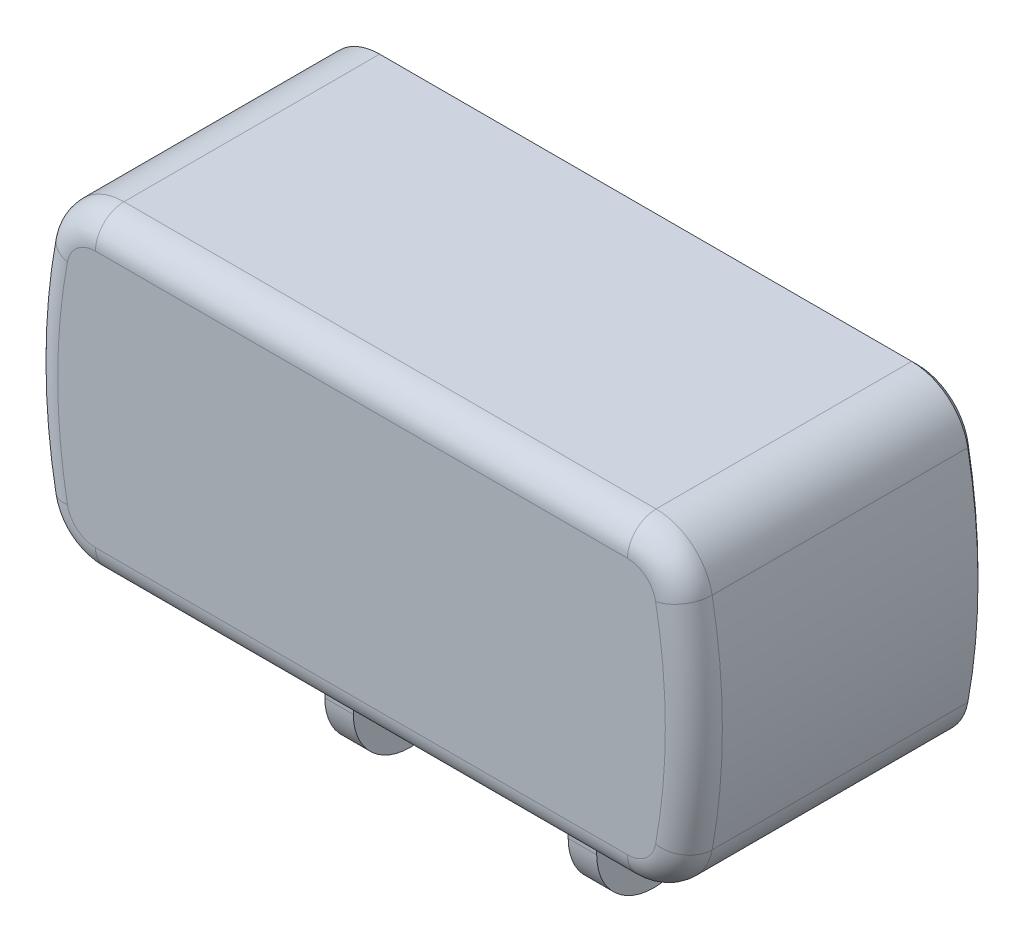
SolidWorks part; units mm, degrees
material "PLA"
ref_plane "Front Plane" through (0, 0, 0) normal (0, 0, 1) x (1, 0, 0)
ref_plane "Top Plane" through (0, 0, 0) normal (0, 1, 0) x (1, 0, 0)
ref_plane "Right Plane" through (0, 0, 0) normal (1, 0, 0) x (0, 0, -1)
sketch "Sketch2" plane through (0, 0, 0) normal (0, 0, 1) x (1, 0, 0)
  line L0 (-47.5, 0) -> (47.5, 0) construction
  line L1 (0, -27.5) -> (0, 27.5) construction
  line L2 (46.625, 27.5) -> (-46.625, 27.5)
  line L3 (46.625, -27.5) -> (-46.625, -27.5)
  arc A0 (-56.4565, 19.3279) -> (-56.4565, -19.3279) centre (47.5, 0) ccw
  arc A1 (-46.625, -27.5) -> (-56.4565, -19.3279) centre (-46.625, -17.5) cw
  arc A2 (-46.625, 27.5) -> (-56.4565, 19.3279) centre (-46.625, 17.5) ccw
  arc A3 (46.625, -27.5) -> (56.4565, -19.3279) centre (46.625, -17.5) ccw
  arc A4 (56.4565, 19.3279) -> (56.4565, -19.3279) centre (-47.5, 0) cw
  arc A5 (46.625, 27.5) -> (56.4565, 19.3279) centre (46.625, 17.5) cw
  point P4 (0, 0)
  point P8 (0, 0)
  dimension "D3" = 0
  dimension "D4" = 10
  dimension "D1" = 95
  dimension "D2" = 55
  dimension "D5" = 46.625
extrude "Boss-Extrude5" add sketch "Sketch2" along normal blind 50.8
fillet "Fillet9" radius 5 8 edges at (-58.238, 0, 50.8) (-53.0172, 25.1902, 50.8) (0, 27.5, 50.8) (53.0172, 25.1902, 50.8) (58.238, 0, 50.8) (53.0172, -25.1902, 50.8) (0, -27.5, 50.8) (-53.0172, -25.1902, 50.8)
sketch "Sketch3" plane through (0, 0, 0) normal (0, 0, -1) x (-1, 0, 0)
  line L0 (-55.738, 0) -> (55.738, 0) construction
  line L1 (0, 0) -> (0, 21.6868) construction
ref_plane "Plane1" through (-18.67, 0, 0) normal (1, 0, 0) x (0, 0, -1)
chamfer "Chamfer1" distance 1 angle 45 8 edges at (0, -27.5, 0) (53.0172, -25.1902, 0) (-53.0172, -25.1902, 0) (58.238, 0, 0) (-58.238, 0, 0) (53.0172, 25.1902, 0) (-53.0172, 25.1902, 0) (0, 27.5, 0)
sketch "Sketch8" plane through (18.825, 0, 0) normal (1, 0, 0) x (0, 0, -1)
  line L2 (-1, -27.5) -> (-45.8, -27.5)
  line L3 (-33.4051, -42.61) -> (-33.4051, -32.61)
  line L4 (-33.4137, -27.5) -> (-38.4137, -27.5)
  line L5 (-38.4137, -27.5) -> (-33.4051, -32.61)
  line L6 (-13.4051, -42.61) -> (-13.4051, -32.61)
  line L7 (-13.4051, -27.5) -> (-8.4051, -27.5)
  line L8 (-8.4051, -27.5) -> (-13.4051, -32.61)
  arc A0 (-33.4051, -42.61) -> (-13.4051, -42.61) centre (-23.4051, -42.61) ccw construction
  arc A2 (-33.4051, -42.61) -> (-13.4051, -42.61) centre (-23.4051, -42.61) ccw
  circle A4 centre (-23.4051, -35.61) radius 1.35
  circle A5 centre (-16.4051, -42.61) radius 1.35
  circle A6 centre (-23.4051, -49.61) radius 1.35
  circle A7 centre (-30.4051, -42.61) radius 1.35
  dimension "D1" = 2.7
  dimension "D2" = 10
  dimension "D3" = 5
  dimension "D4" = 5
extrude "Boss-Extrude6" add sketch "Sketch8" along normal blind 5
mirror "Mirror1" about plane through (0, 0, 0) normal (1, 0, 0) of "Boss-Extrude6"
sketch "Sketch4" plane through (0, 0, 0) normal (0, 0, -1) x (-1, 0, 0)
  line L1 (0, 27.5) -> (0, -27.5) construction
  line L3 (-46.625, 27.5) -> (46.625, 27.5) construction
  line L10 (46.625, -27.5) -> (-46.625, -27.5) construction
  line L11 (-58.238, 0) -> (58.238, 0) construction
  line L13 (-40.665, 14.165) -> (40.665, 14.165)
  line L14 (-45.665, 9.165) -> (-45.665, -9.165)
  line L15 (-40.665, -14.165) -> (40.665, -14.165)
  line L16 (45.665, 9.165) -> (45.665, -9.165)
  arc A0 (-56.4565, 19.3279) -> (-56.4565, -19.3279) centre (47.5, 0) ccw construction
  arc A1 (56.4565, -19.3279) -> (56.4565, 19.3279) centre (-47.5, 0) ccw construction
  arc A2 (40.665, -14.165) -> (45.665, -9.165) centre (40.665, -9.165) ccw
  arc A3 (-45.665, -9.165) -> (-40.665, -14.165) centre (-40.665, -9.165) ccw
  arc A4 (-40.665, 14.165) -> (-45.665, 9.165) centre (-40.665, 9.165) ccw
  arc A5 (40.665, 14.165) -> (45.665, 9.165) centre (40.665, 9.165) cw
  point P18 (0, 14.165)
  point P19 (-45.665, 0)
  point P24 (-45.665, -14.165)
  point P27 (-45.665, 14.165)
  point P30 (45.665, 14.165)
  dimension "D3" = 5
  dimension "D1" = 28.33
  dimension "D2" = 91.33
extrude "Cut-Extrude3" cut sketch "Sketch4" against normal blind 20
chamfer "Chamfer2" distance 20 angle 2 8 edges at (-45.665, 0, 20) (-44.2005, 12.7005, 20) (-44.2005, -12.7005, 20) (0, 14.165, 20) (0, -14.165, 20) (44.2005, 12.7005, 20) (44.2005, -12.7005, 20) (45.665, 0, 20) first distance on face at (-45.665, 0, 10) first distance on face at (-43.6828, 12.1828, 10) first distance on face at (-43.6828, -12.1828, 10) first distance on face at (0, 14.165, 10) first distance on face at (0, -14.165, 10) first distance on face at (43.6828, 12.1828, 10) first distance on face at (43.6828, -12.1828, 10) first distance on face at (45.665, 0, 10)
sketch "Sketch15" plane through (0, 0, 0) normal (0, 0, -1) x (-1, 0, 0)
  circle A0 centre (-48.2893, 18.5609) radius 1.35
  circle A2 centre (48.2893, -18.5609) radius 1.35
  circle A3 centre (48.2893, 18.5609) radius 1.35
  circle A4 centre (-48.2893, -18.5609) radius 1.35
  dimension "D1" = 2.7
extrude "Cut-Extrude4" cut sketch "Sketch15" against normal blind 5
